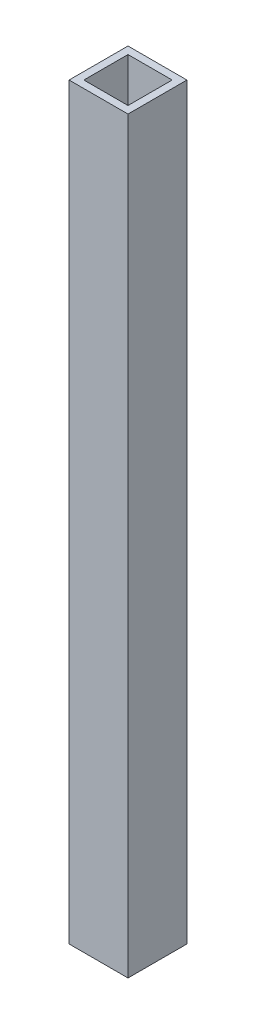
SolidWorks part; units mm, degrees
material "Thornel Mat VMA"
ref_plane "Front Plane" through (0, 0, 0) normal (0, 0, 1) x (1, 0, 0)
ref_plane "Top Plane" through (0, 0, 0) normal (0, 1, 0) x (1, 0, 0)
ref_plane "Right Plane" through (0, 0, 0) normal (1, 0, 0) x (0, 0, -1)
sketch "Sketch1" plane through (0, 0, 0) normal (0, 1, 0) x (1, 0, 0)
  line L1 (0, 0) -> (8.001, 0)
  line L2 (0, 0) -> (0, 8.001)
  line L3 (0, 8.001) -> (8.001, 8.001)
  line L4 (8.001, 0) -> (8.001, 8.001)
  dimension "D1" = 8.001
  dimension "D2" = 8.001
extrude "Boss-Extrude1" add sketch "Sketch1" along normal blind 101.6
sketch "Sketch2" plane through (0, 101.6, 0) normal (0, 1, 0) x (1, 0, 0)
  line L1 (1.0033, 6.9977) -> (6.9977, 6.9977)
  line L2 (1.0033, 6.9977) -> (1.0033, 1.0033)
  line L3 (1.0033, 1.0033) -> (6.9977, 1.0033)
  line L4 (6.9977, 6.9977) -> (6.9977, 1.0033)
  line L5 (8.001, 8.001) -> (0, 8.001) construction
  line L6 (0, 8.001) -> (0, 0) construction
  dimension "D1" = 5.9944
  dimension "D2" = 5.9944
  dimension "D3" = 1.0033
  dimension "D4" = 1.0033
extrude "Cut-Extrude1" cut sketch "Sketch2" against normal through all
